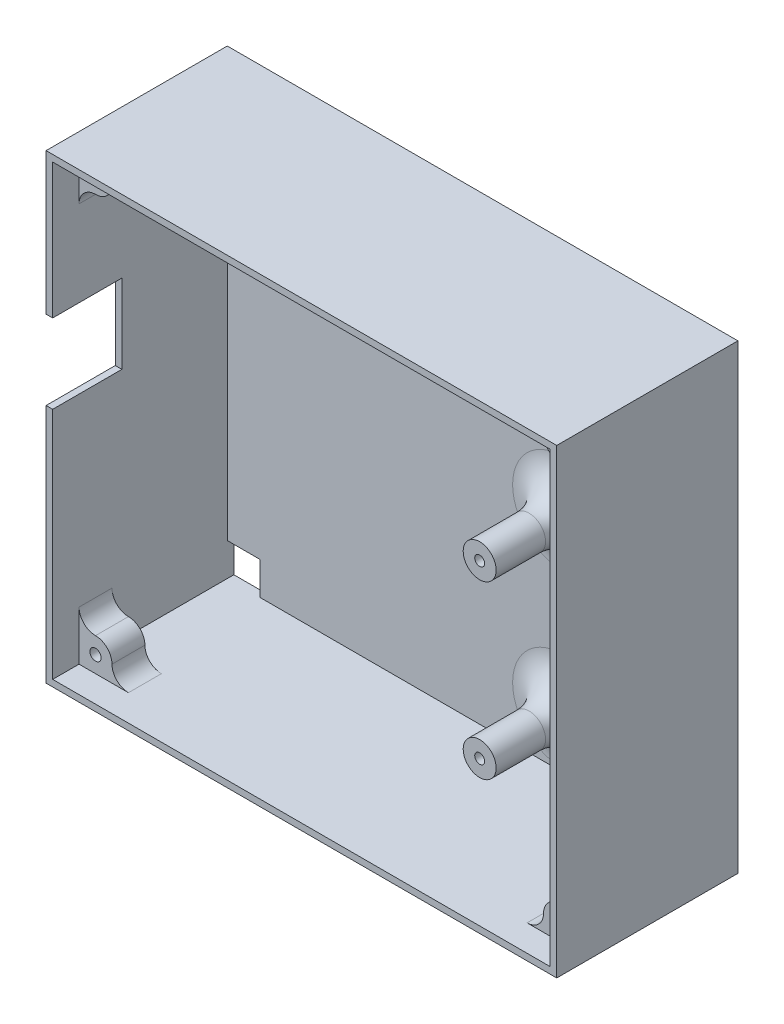
SolidWorks part; units mm, degrees
ref_plane "Ebene vorne" through (0, 0, 0) normal (0, 0, 1) x (1, 0, 0)
ref_plane "Ebene oben" through (0, 0, 0) normal (0, 1, 0) x (1, 0, 0)
ref_plane "Ebene rechts" through (0, 0, 0) normal (1, 0, 0) x (0, 0, -1)
sketch "Skizze1" plane through (0, 0, 0) normal (0, 0, 1) x (1, 0, 0)
  line L1 (-77.5, -70) -> (77.5, -70)
  line L2 (-77.5, -70) -> (-77.5, 70)
  line L3 (-77.5, 70) -> (77.5, 70)
  line L4 (77.5, -70) -> (77.5, 70)
  line L5 (-77.5, -70) -> (77.5, 70) construction
  line L6 (-77.5, 70) -> (77.5, -70) construction
  point P0 (0, 0)
extrude "Aufsatz-Linear austragen2" add sketch "Skizze1" along normal blind 55
shell "Wandung3" thickness 2
sketch "Skizze2" plane through (-77.5, 0, 0) normal (-1, 0, 0) x (0, 0, 1)
  line L0 (55, 70) -> (55, -70) construction
  line L1 (55, 3) -> (34, 3)
  line L2 (55, 3) -> (55, 27)
  line L3 (55, 27) -> (34, 27)
  line L4 (34, 3) -> (34, 27)
  line L5 (55, 70) -> (0, 70) construction
  point P8 (34, 15)
  dimension "D1" = 55
extrude "Schnitt-Linear austragen1" cut sketch "Skizze2" against normal blind 2
sketch "Skizze3" plane through (0, 0, 2) normal (0, 0, 1) x (1, 0, 0)
  circle A0 centre (26.1113, -52) radius 5
  circle A1 centre (26.1113, 0) radius 5
  dimension "D1" = 3
  dimension "D2" = 52
extrude "Aufsatz-Linear austragen5" add sketch "Skizze3" along normal blind 25
fillet "Verrundung1" radius 10 2 edges at (21.1113, -52, 2) (21.1113, 0, 2)
hole_wizard "Ø3.0 (3) Durchmesser Bohrung1" positions "Skizze4" profile "Skizze5" hole size "Ø3.0" standard "ANSI Metrisch"
sketch "Skizze4" plane through (0, 0, 27) normal (0, 0, 1) x (1, 0, 0)
  point P0 (26.1113, 0)
  point P3 (26.1113, -52)
sketch "Skizze5" plane through (26.1113, 0, 27) normal (1, 0, 0) x (0, -1, 0)
  line L0 (0, 0) -> (0, 20.9013)
  line L1 (0, 20.9013) -> (1.5, 20)
  line L2 (1.5, 20) -> (1.5, 0)
  line L5 (1.5, 0) -> (0, 0)
  line L10 (0, 20.9013) -> (-1.5, 20) construction
  line L11 (0, -6.35) -> (0, 107.95) construction
  dimension "Bohrerdurchmesser" = 3
  dimension "Bohrungstiefe" = 20
  dimension "Spitzenwinkel" = 118
sketch "Skizze6" plane through (0, 0, 2) normal (0, 0, 1) x (1, 0, 0)
  line L1 (-75.5, -68) -> (-65.5, -68)
  line L2 (-75.5, -68) -> (-75.5, -58)
  line L3 (-75.5, -58) -> (-65.5, -58)
  line L4 (-65.5, -68) -> (-65.5, -58)
  line L5 (75.5, -68) -> (65.5, -68)
  line L6 (75.5, -68) -> (75.5, -58)
  line L7 (75.5, -58) -> (65.5, -58)
  line L8 (65.5, -68) -> (65.5, -58)
  line L9 (75.5, 68) -> (65.5, 68)
  line L10 (75.5, 68) -> (75.5, 58)
  line L11 (75.5, 58) -> (65.5, 58)
  line L12 (65.5, 68) -> (65.5, 58)
  line L13 (-75.5, 68) -> (-65.5, 68)
  line L14 (-75.5, 68) -> (-75.5, 58)
  line L15 (-75.5, 58) -> (-65.5, 58)
  line L16 (-65.5, 68) -> (-65.5, 58)
extrude "Schnitt-Linear austragen2" cut sketch "Skizze6" against normal up to next
sketch3d "3D-Skizze1"
  line L0 (-75.5, 68, 55) -> (-75.5, 68, 0) construction
  line L1 (-75.5, 68, 47) -> (-65.5, 68, 47)
  line L2 (-75.5, 68, 47) -> (-75.5, 58, 47)
  line L3 (-75.5, 58, 47) -> (-65.5, 58, 47)
  line L4 (-65.5, 68, 47) -> (-65.5, 58, 47)
  line L5 (75.5, 68, 55) -> (75.5, 68, 0) construction
  line L6 (75.5, 68, 47) -> (65.5, 68, 47)
  line L7 (75.5, 68, 47) -> (75.5, 58, 47)
  line L8 (75.5, 58, 47) -> (65.5, 58, 47)
  line L9 (65.5, 68, 47) -> (65.5, 58, 47)
  line L10 (75.5, -68, 55) -> (75.5, -68, 0) construction
  line L11 (75.5, -68, 47) -> (65.5, -68, 47)
  line L12 (75.5, -68, 47) -> (75.5, -58, 47)
  line L13 (75.5, -58, 47) -> (65.5, -58, 47)
  line L14 (65.5, -68, 47) -> (65.5, -58, 47)
  line L15 (-75.5, -68, 55) -> (-75.5, -68, 0) construction
  line L16 (-75.5, -68, 47) -> (-65.5, -68, 47)
  line L17 (-75.5, -68, 47) -> (-75.5, -58, 47)
  line L18 (-75.5, -58, 47) -> (-65.5, -58, 47)
  line L19 (-65.5, -68, 47) -> (-65.5, -58, 47)
  dimension "D1" = 8
extrude "Aufsatz-Linear austragen7" add sketch "3D-Skizze1" along a picked direction on the side against the normal blind 10
fillet "Verrundung3" radius 5 12 edges
hole_wizard "Ø3.4 (3.4) Durchmesser Bohrung1" positions "Skizze10" profile "Skizze11" hole size "Ø3.4" standard "ANSI Metrisch" end condition up to next
sketch "Skizze10" plane through (0, 0, 47) normal (0, 0, 1) x (1, 0, 0)
  point P0 (70.5, 63)
  point P3 (70.5, -63)
  point P6 (-70.5, -63)
  point P9 (-70.5, 63)
sketch "Skizze11" plane through (70.5, 63, 47) normal (1, 0, 0) x (0, -1, 0)
  line L0 (0, 0) -> (0, 10)
  line L1 (0, 10) -> (1.7, 10)
  line L2 (1.7, 10) -> (1.7, 0)
  line L5 (1.7, 0) -> (0, 0)
  line L11 (0, -6.35) -> (0, 107.95) construction
  dimension "Bohrerdurchmesser" = 3.4
  dimension "Bohrungstiefe" = 10
sketch "Skizze12" plane through (0, 0, 2) normal (0, 0, 1) x (1, 0, 0)
  circle A0 centre (51.7981, 44.1861) radius 5
  circle A1 centre (-8.2019, 44.1861) radius 5
  dimension "D2" = 10
  dimension "D3" = 10
  dimension "D1" = 60
extrude "Aufsatz-Linear austragen8" add sketch "Skizze12" along normal blind 10
fillet "Verrundung4" radius 5 2 edges at (-13.2019, 44.1861, 2) (46.7981, 44.1861, 2)
hole_wizard "Ø3.4 (3.4) Durchmesser Bohrung2" positions "Skizze13" profile "Skizze15" hole size "Ø3.4" standard "ANSI Metrisch"
sketch "Skizze13" plane through (0, 0, 12) normal (0, 0, 1) x (1, 0, 0)
  point P0 (51.7981, 44.1861)
  point P3 (-8.2019, 44.1861)
sketch "Skizze15" plane through (51.7981, 44.1861, 12) normal (1, 0, 0) x (0, -1, 0)
  line L0 (0, 0) -> (0, 11.0215)
  line L1 (0, 11.0215) -> (1.7, 10)
  line L2 (1.7, 10) -> (1.7, 0)
  line L5 (1.7, 0) -> (0, 0)
  line L10 (0, 11.0215) -> (-1.7, 10) construction
  line L11 (0, -6.35) -> (0, 107.95) construction
  dimension "Bohrerdurchmesser" = 3.4
  dimension "Bohrungstiefe" = 10
  dimension "Spitzenwinkel" = 118
